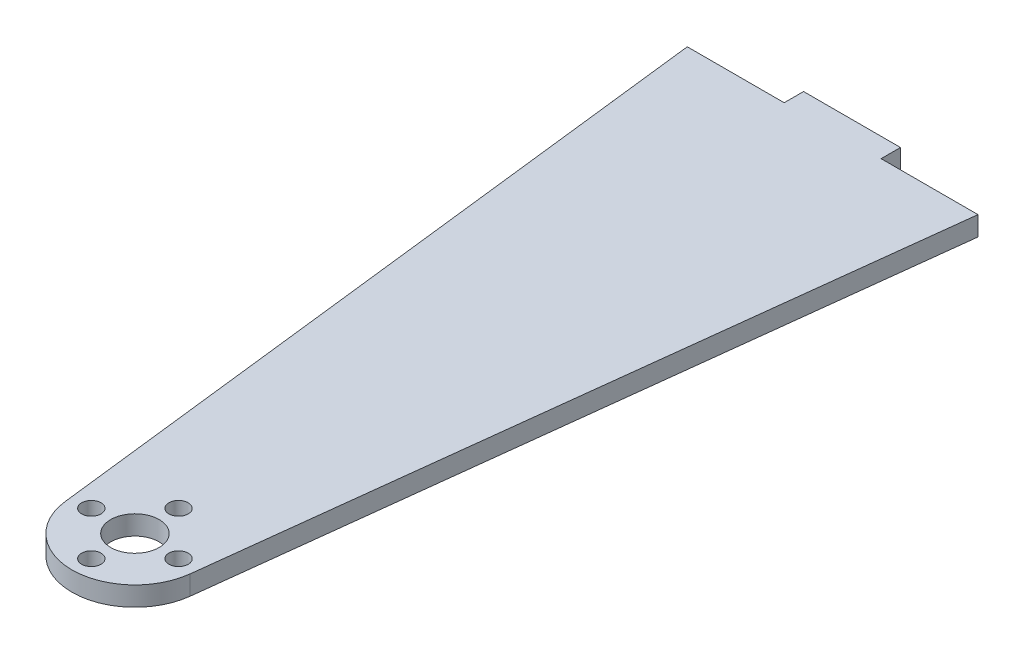
SolidWorks part; units mm, degrees
material "Pine"
ref_plane "Front Plane" through (0, 0, 0) normal (0, 0, 1) x (1, 0, 0)
ref_plane "Top Plane" through (0, 0, 0) normal (0, 1, 0) x (1, 0, 0)
ref_plane "Right Plane" through (0, 0, 0) normal (1, 0, 0) x (0, 0, -1)
sketch "Sketch2" plane through (0, 69.85, 0) normal (0, 1, 0) x (1, 0, 0)
  line L0 (-103.1875, 0) -> (103.1875, 0) construction
  line L1 (-15.875, 6.35) -> (15.875, 6.35)
  line L4 (15.875, 6.35) -> (15.875, 0)
  line L9 (-47.625, 0) -> (-20.4966, -231.007)
  line L10 (-15.875, 0) -> (-47.625, 0)
  line L15 (0, 0) -> (0, -228.6) construction
  line L16 (47.625, 0) -> (15.875, 0)
  line L23 (-15.875, 6.35) -> (-15.875, 0)
  line L24 (47.625, 0) -> (20.4966, -231.007)
  line L26 (-25.4, 0) -> (-9.525, 0) construction
  arc A6 (-20.4966, -231.007) -> (20.4966, -231.007) centre (0, -228.6) ccw
  circle A7 centre (0, -228.6) radius 7.9375
  circle A8 centre (0, -214.3125) radius 3.175
  circle A9 centre (14.2875, -228.6) radius 3.175
  circle A10 centre (0, -242.8875) radius 3.175
  circle A11 centre (-14.2875, -228.6) radius 3.175
  arc A12 (-20.2897, -232.3729) -> (20.2897, -232.3729) centre (0, -228.6) ccw construction
  circle A13 centre (0, -228.6) radius 7.9375 construction
  circle A14 centre (-14.2875, -228.6) radius 3.175 construction
  circle A15 centre (14.2875, -228.6) radius 3.175 construction
  circle A16 centre (0, -242.8875) radius 3.175 construction
  circle A17 centre (0, -214.3125) radius 3.175 construction
  dimension "D1" = 95.25
extrude "Boss-Extrude1" add sketch "Sketch2" along normal blind 6.35
